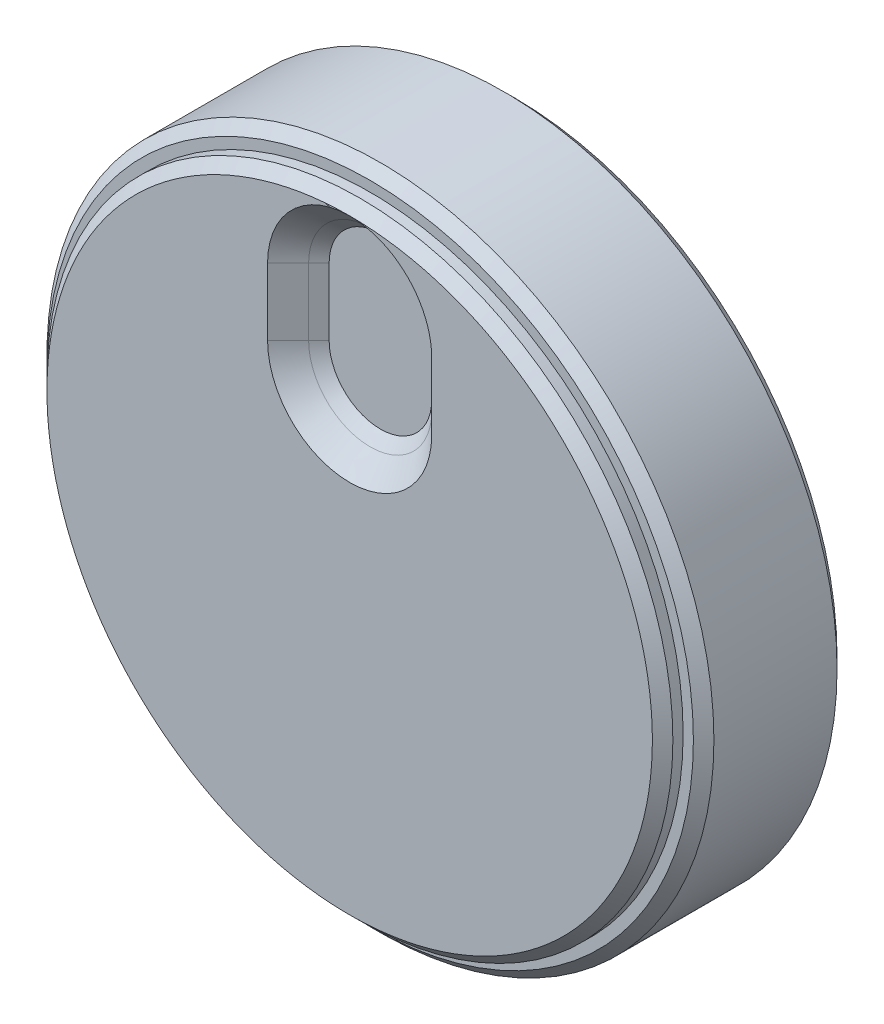
SolidWorks part; units mm, degrees
ref_plane "Alzado" through (0, 0, 0) normal (0, 0, 1) x (1, 0, 0)
ref_plane "Planta" through (0, 0, 0) normal (0, 1, 0) x (1, 0, 0)
ref_plane "Vista lateral" through (0, 0, 0) normal (1, 0, 0) x (0, 0, -1)
sketch "Croquis1" plane through (0, 0, 0) normal (0, 0, 1) x (1, 0, 0)
  circle A0 centre (0, 0) radius 3
  circle A1 centre (0, 0) radius 32.5
  dimension "D1" = 6
  dimension "D2" = 65
extrude "Saliente-Extruir1" add sketch "Croquis1" along normal blind 14
sketch "Croquis2" plane through (0, 0, 0) normal (0, 0, -1) x (-1, 0, 0)
  circle A0 centre (0, 0) radius 17.5
  dimension "D1" = 35
extrude "Cortar-Extruir1" cut sketch "Croquis2" against normal blind 3
sketch "Croquis3" plane through (0, 0, 14) normal (0, 0, 1) x (1, 0, 0)
  circle A0 centre (0, 0) radius 30.5
  dimension "D1" = 61
extrude "Saliente-Extruir2" add sketch "Croquis3" along normal blind 2
chamfer "Chaflán1" distance 1 angle 45 3 edges at (30.5, 0, 16) (32.5, 0, 0) (32.5, 0, 14)
sketch "Croquis4" plane through (0, 0, 16) normal (0, 0, 1) x (1, 0, 0)
  line L0 (0, 0) -> (0, 29.5) construction
  line L1 (0, 21.5) -> (0, 15) construction
  line L2 (6, 21.5) -> (6, 15)
  line L3 (-6, 21.5) -> (-6, 15)
  circle A0 centre (0, 0) radius 29.5 construction
  arc A1 (6, 21.5) -> (-6, 21.5) centre (0, 21.5) ccw
  arc A2 (-6, 15) -> (6, 15) centre (0, 15) ccw
  point P8 (0, 18.25)
  point P13 (0, 9)
  point P14 (0, 27.5)
  dimension "D1" = 9
  dimension "D2" = 18.5
  dimension "D3" = 12
extrude "Cortar-Extruir2" cut sketch "Croquis4" against normal blind 3
chamfer "Chaflán2" distance 2 angle 45 4 edges at (6, 18.25, 16) (0, 27.5, 16) (0, 9, 16) (-6, 18.25, 16)
sketch "Croquis5" plane through (0, 0, 13) normal (0, 0, 1) x (1, 0, 0)
  line L0 (5, 15) -> (5, 21.5)
  line L1 (-5, 21.5) -> (-5, 15)
  line L2 (-6, 21.5) -> (-6, 15)
  line L3 (6, 15) -> (6, 21.5)
  line L4 (-6, 21.5) -> (-6, 15)
  line L5 (6, 15) -> (6, 21.5)
  arc A0 (-5, 15) -> (5, 15) centre (0, 15) ccw
  arc A1 (5, 21.5) -> (-5, 21.5) centre (0, 21.5) ccw
  arc A2 (6, 21.5) -> (-6, 21.5) centre (0, 21.5) ccw
  arc A3 (-6, 15) -> (6, 15) centre (0, 15) ccw
  arc A4 (6, 21.5) -> (-6, 21.5) centre (0, 21.5) ccw
  arc A5 (-6, 15) -> (6, 15) centre (0, 15) ccw
  dimension "D1" = 0
  dimension "D2" = 1
extrude "Saliente-Extruir3" add sketch "Croquis5" along normal blind 1
chamfer "Chaflán3" distance 1 angle 45 4 edges at (5, 18.25, 14) (0, 26.5, 14) (0, 10, 14) (-5, 18.25, 14)
